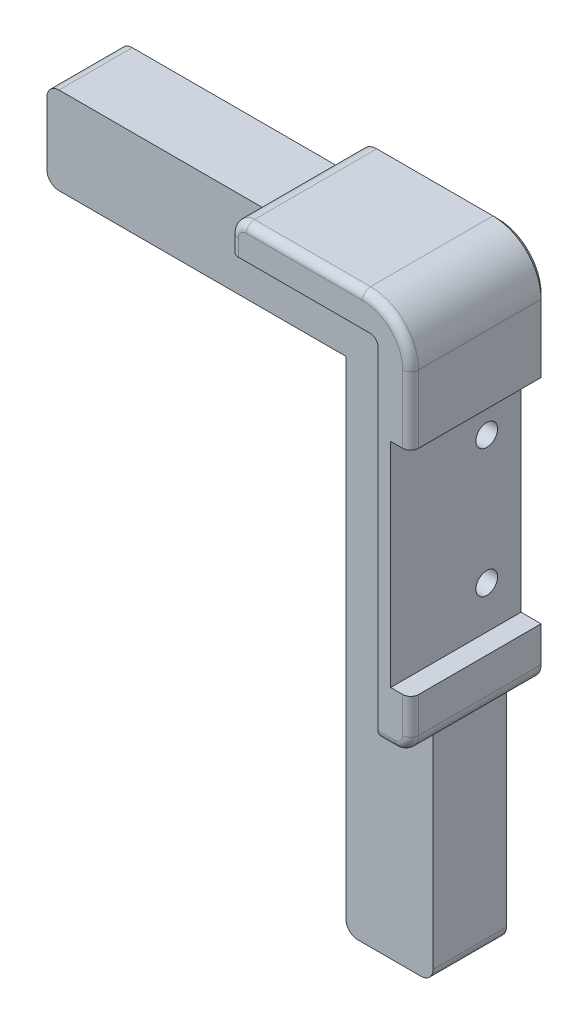
SolidWorks part; units mm, degrees
ref_plane "Front Plane" through (0, 0, 0) normal (0, 0, 1) x (1, 0, 0)
ref_plane "Top Plane" through (0, 0, 0) normal (0, 1, 0) x (1, 0, 0)
ref_plane "Right Plane" through (0, 0, 0) normal (1, 0, 0) x (0, 0, -1)
ref_plane "PZ 20.375" through (0, 0, 20.375) normal (0, 0, 1) x (1, 0, 0)
sketch "body and tongues sketch" plane through (0, 0, 20.375) normal (0, 0, 1) x (1, 0, 0)
  line L0 (4.42, 7.07) -> (-18.08, 7.07)
  line L1 (-18.08, 7.07) -> (-18.08, 2.75)
  line L2 (-18.08, 2.75) -> (-48.08, 2.75)
  line L3 (-48.08, 2.75) -> (-48.08, -8.13)
  line L4 (-48.08, -8.13) -> (-10.78, -8.13)
  line L5 (-10.78, -8.13) -> (-10.78, -70.43)
  line L6 (-10.78, -70.43) -> (0.1, -70.43)
  line L7 (0.1, -70.43) -> (0.1, -40.43)
  line L8 (0.1, -40.43) -> (4.42, -40.43)
  line L9 (4.42, -40.43) -> (4.42, 7.07)
extrude "body and tongues" add sketch "body and tongues sketch" along normal mid plane 9.75
ref_plane "PZ 23.935" through (0, 0, 23.935) normal (0, 0, 1) x (1, 0, 0)
sketch "rim sketch" plane through (0, 0, 23.935) normal (0, 0, 1) x (1, 0, 0)
  line L0 (4.42, 7.07) -> (-18.08, 7.07)
  line L1 (-18.08, 7.07) -> (-18.08, 3)
  line L2 (-18.08, 3) -> (0.35, 3)
  line L3 (0.35, 3) -> (0.35, -40.43)
  line L4 (0.35, -40.43) -> (4.42, -40.43)
  line L5 (4.42, -40.43) -> (4.42, 7.07)
extrude "rim" add sketch "rim sketch" along normal mid plane 16.87
sketch "bracket seat sketch" plane through (0, 0, 23.935) normal (0, 0, 1) x (1, 0, 0)
  line L0 (1.92, -34) -> (5.42, -34)
  line L1 (5.42, -34) -> (5.42, -7.4)
  line L2 (5.42, -7.4) -> (1.92, -7.4)
  line L3 (1.92, -7.4) -> (1.92, -34)
extrude "bracket seat" cut sketch "bracket seat sketch" against normal mid plane 18.87
ref_plane "PX -2.580" through (-2.58, 0, 0) normal (1, 0, 0) x (0, 0, -1)
sketch "screw pilots sketch" plane through (-2.58, 0, 0) normal (1, 0, 0) x (0, 0, -1)
  circle A0 centre (-20.375, -28.7) radius 1.35
  circle A1 centre (-20.375, -12.7) radius 1.35
extrude "screw pilots" cut sketch "screw pilots sketch" against normal mid plane 11
fillet "bumper corner" radius 6 1 edges at (4.42, 7.07, 23.935) tangent propagation no
fillet "inside corner of the rim" radius 1 1 edges at (0.35, 3, 28.81) tangent propagation no
fillet "rim ends" radius 2 2 edges at (-18.08, 7.07, 23.935) (4.42, -40.43, 23.935) tangent propagation no
fillet "tongue lead-in" radius 1.5 4 edges at (-48.08, -8.13, 20.375) (-48.08, 2.75, 20.375) (-10.78, -70.43, 20.375) (0.1, -70.43, 20.375) tangent propagation no
fillet "rim top edge" radius 1 7 edges at (4.42, -36.215, 32.37) (2.6626, 5.3126, 32.37) (-18.08, 4.035, 32.37) (-17.4942, 6.4842, 32.37) (1.385, -40.43, 32.37) (3.8342, -39.8442, 32.37) (-8.83, 7.07, 32.37)
chamfer "bed face chamfer" distance 0.6 angle 45 20 edges at (-10.78, -38.53, 15.5) (-10.3407, -69.9907, 15.5) (-5.34, -70.43, 15.5) (-0.3393, -69.9907, 15.5) (0.1, -54.68, 15.5) (1.26, -40.43, 15.5) (3.8342, -39.8442, 15.5) (4.42, -3.165, 15.5) (3.17, -34, 15.5) (1.92, -20.7, 15.5) (3.17, -7.4, 15.5) (2.6626, 5.3126, 15.5) (-8.83, 7.07, 15.5) (-17.4942, 6.4842, 15.5) (-18.08, 3.91, 15.5) (-32.33, 2.75, 15.5) (-47.6407, 2.3107, 15.5) (-48.08, -2.69, 15.5) (-47.6407, -7.6907, 15.5) (-28.68, -8.13, 15.5)
equation "\"diffL\" = 608.8mm"
equation "\"diffW\" = 329.4mm"
equation "\"diffT\" = 2.9mm"
equation "\"chanSlotW\" = 12.9mm"
equation "\"chanSlotDepth\" = 11.13mm"
equation "\"chanFloor\" = 1.57mm"
equation "\"chanLeg\" = 12.7mm"
equation "\"lightL\" = 605mm"
equation "\"lightW\" = 331mm"
equation "\"lightH\" = 92mm"
equation "\"lightSideFlat\" = 30mm"
equation "\"lightSlopeLen\" = 33.1mm"
equation "\"lightWingDepth\" = 47.9mm"
equation "\"lightWingFlat\" = 90.2mm"
equation "\"lightChanW\" = 99.6mm"
equation "\"lightChanStand\" = 44.1mm"
equation "\"insFlangeD\" = 12.3mm"
equation "\"insFromEnd\" = 20.7mm"
equation "\"insUpSlope\" = 20.8mm"
equation "\"gaugeH\" = 10mm"
equation "\"gaugeStepLen\" = 14mm"
equation "\"gaugeStepW0\" = 13.1mm"
equation "\"gaugeStepDW\" = 0.2mm"
equation "\"gaugeSteps\" = 5mm"
equation "\"gaugeHandleLen\" = 30mm"
equation "\"gaugeHandleW\" = 24mm"
equation "\"gaugeSlot0\" = 3mm"
equation "\"gaugeSlotD\" = 0.1mm"
equation "\"gaugeSlotDepth\" = 8mm"
equation "\"gap\" = 25.4mm"
equation "\"edgeL\" = 1mm"
equation "\"edgeW\" = 0.75mm"
equation "\"proud\" = 1.5mm"
equation "\"seatClr\" = 0.15mm"
equation "\"tongueClrZ\" = 0.1mm"
equation "\"tongueClrX\" = 0.25mm"
equation "\"tongueLen\" = 30mm"
equation "\"armSide\" = 45mm"
equation "\"armEnd\" = 20mm"
equation "\"cornerCham\" = 3mm"
equation "\"brkW\" = 26mm"
equation "\"brkT\" = 7mm"
equation "\"brkSeatClr\" = 0.2mm"
equation "\"brkScrewSpan\" = 16mm"
equation "\"pilotD\" = 2.7mm"
equation "\"pilotDepth\" = 10mm"
equation "\"screwClrD\" = 3.9mm"
equation "\"jogBelow\" = 4mm"
equation "\"padT\" = 7mm"
equation "\"padLen\" = 31mm"
equation "\"m6Clr\" = 7mm"
equation "\"m6Slot\" = 3mm"
equation "\"flangeRelD\" = 17mm"
equation "\"flangeRelDepth\" = 1.5mm"
equation "\"relLen\" = 7mm"
equation "\"relDepth\" = 4mm"
equation "\"relLand\" = 2mm"
equation "\"knockN\" = 100mm"
equation "\"petgcfE\" = 3000mm"
equation "\"mockExtent\" = 110mm"
equation "\"relZnear\" = 9.4mm"
equation "\"relZfar\" = 23.4mm"
equation "\"headD\" = 8mm"
equation "\"headH\" = 2.5mm"
equation "\"headFromEnd\" = 6.8mm"
equation "\"headBack\" = 16.4mm"
equation "\"sideClr\" = 0.4mm"
equation "\"cornerRelR\" = 1.5mm"
equation "\"cornerRelBack\" = 0.6mm"
equation "\"endHeadH\" = 2.8mm"
equation "\"footClr\" = 1.2mm"
equation "\"footEndClr\" = 3.5mm"
equation "\"footLift\" = 6mm"
equation "\"footBlockClr\" = 0.5mm"
equation "\"footBack\" = 50mm"
equation "\"footFwd\" = 10mm"
equation "\"footBraceEnd\" = 3mm"
equation "\"footLoadN\" = 25mm"
equation "\"spacerLen\" = 60mm"
equation "\"spacerShort\" = 0.5mm"
equation "\"spacerCham\" = 0.8mm"
equation "\"spacerPerSide\" = 3mm"
equation "\"spacerPerEnd\" = 1mm"
equation "\"toolR\" = 9mm"
equation "\"visR\" = 4mm"
equation "\"edgeR\" = 1mm"
equation "\"bendOutR\" = 5mm"
equation "\"insideR\" = 2.5mm"
equation "\"footCornerR\" = 10mm"
equation "\"footFrontR\" = 8mm"
equation "\"braceKinkR\" = 12mm"
equation "\"bedCham\" = 1mm"
equation "\"bedChamSmall\" = 0.6mm"
equation "\"soleTopR\" = 2mm"
equation "\"cornerR\" = 6mm"
equation "\"rimInR\" = 1mm"
equation "\"insFlangeH\" = 1mm"
